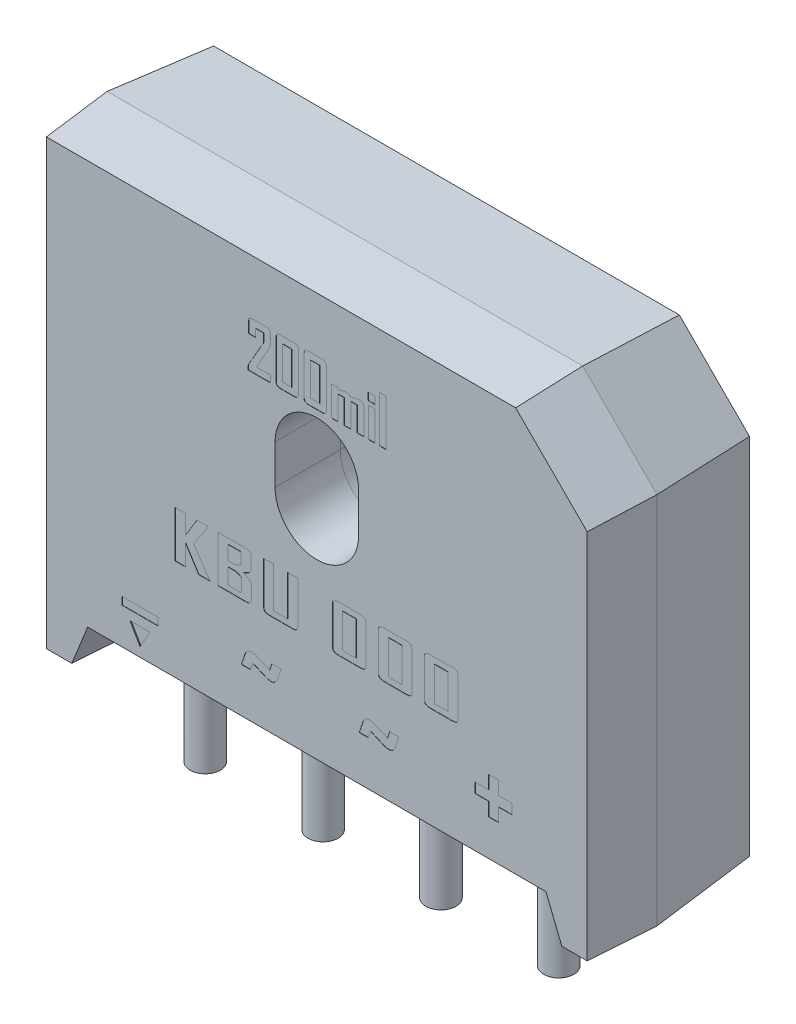
SolidWorks part; units mm, degrees
ref_plane "Спереди" through (0, 0, 0) normal (0, 0, 1) x (1, 0, 0)
ref_plane "Сверху" through (0, 0, 0) normal (0, 1, 0) x (1, 0, 0)
ref_plane "Справа" through (0, 0, 0) normal (1, 0, 0) x (0, 0, -1)
sketch "Sketch1" plane through (0, 0, 0) normal (0, 0, 1) x (1, 0, 0)
  line L0 (0, 19.3) -> (0, 0) construction
  line L1 (-4.23, 19.3) -> (19.47, 19.3)
  line L2 (-4.23, 19.3) -> (-4.23, 0)
  line L3 (-4.23, 0) -> (19.47, 0)
  line L4 (19.47, 19.3) -> (19.47, 0)
  line L5 (-4.23, 19.3) -> (19.47, 0) construction
  point P7 (7.62, 9.65)
  dimension "L" = 23.7
  dimension "H" = 19.3
  dimension "PIN_L1_H" = 0
  dimension "PIN_START" = 7.62
extrude "BODY_MAIN" add sketch "Sketch1" along normal blind 2.81 and the other way blind 4.29
sketch "Sketch8" plane through (0, 0, 2.81) normal (0, 0, 1) x (1, 0, 0)
  line L0 (7.62, 12.65) -> (7.62, 10.95) construction
  line L1 (9.42, 12.65) -> (9.42, 10.95)
  line L2 (5.82, 12.65) -> (5.82, 10.95)
  line L3 (19.47, 19.3) -> (-4.23, 19.3) construction
  line L4 (-4.23, 11.8) -> (19.47, 11.8) construction
  line L5 (-4.23, 19.3) -> (-4.23, 0) construction
  line L6 (19.47, 0) -> (19.47, 19.3) construction
  arc A0 (9.42, 12.65) -> (5.82, 12.65) centre (7.62, 12.65) ccw
  arc A1 (5.82, 10.95) -> (9.42, 10.95) centre (7.62, 10.95) ccw
  point P2 (7.62, 11.8)
  dimension "D1" = 7.5
  dimension "D2" = 3.6
  dimension "D3" = 1.7
extrude "Cut-Extrude1" cut sketch "Sketch8" against normal up to next
sketch "Sketch18" plane through (0, 0, 2.81) normal (0, 0, 1) x (1, 0, 0)
  line L0 (7.62, 0) -> (7.62, 19.3) construction
  line L1 (-4.23, 0) -> (19.47, 0) construction
  line L2 (17.364, 1.5) -> (-2.124, 1.5)
  line L3 (19.47, 19.3) -> (-4.23, 19.3) construction
  line L4 (-2.124, 1.5) -> (-2.73, 0)
  line L5 (-2.73, 0) -> (-2.73, -1)
  line L6 (-2.73, -1) -> (17.97, -1)
  line L7 (7.62, 0) -> (7.62, -1) construction
  line L8 (-4.23, 19.3) -> (-4.23, 0) construction
  line L9 (17.364, 1.5) -> (17.97, 0)
  line L10 (17.97, 0) -> (17.97, -1)
  point P14 (7.62, 1.5)
  dimension "D1" = 17.8
  dimension "D2" = 68
  dimension "D3" = 1.5
  dimension "D4" = 1
extrude "Cut-Extrude2" cut sketch "Sketch18" against normal through all
chamfer "BODY_Chamfer" distance 3.2 angle 45 1 edges at (19.47, 19.3, -0.74)
chamfer "BODY_Chamfer1" distance 2.81 angle 4 7 edges at (6.02, 19.3, 2.81) (19.47, 8.05, 2.81) (-4.23, 9.65, 2.81) (17.87, 17.7, 2.81) (17.667, 0.75, 2.81) (7.62, 1.5, 2.81) (-2.427, 0.75, 2.81) first distance on face at (6.02, 19.3, -0.74) first distance on face at (19.47, 8.05, -0.74) first distance on face at (-4.23, 9.65, -0.74) first distance on face at (17.87, 17.7, -0.74) first distance on face at (17.667, 0.75, -0.74) first distance on face at (7.62, 1.5, -0.74) first distance on face at (-2.427, 0.75, -0.74)
chamfer "BODY_Chamfer2" distance 4.29 angle 4 13 edges at (18.72, 0, -4.29) (-3.48, 0, -4.29) (19.47, 8.05, -4.29) (6.02, 19.3, -4.29) (-4.23, 9.65, -4.29) (17.87, 17.7, -4.29) (7.62, 9.15, -4.29) (5.82, 11.8, -4.29) (7.62, 14.45, -4.29) (9.42, 11.8, -4.29) (-2.427, 0.75, -4.29) (7.62, 1.5, -4.29) (17.667, 0.75, -4.29) first distance on face at (18.7226, 0, -0.4933) first distance on face at (-3.4826, 0, -0.4933) first distance on face at (19.47, 8.05, -2.145) first distance on face at (6.02, 19.3, -2.145) first distance on face at (-4.23, 9.65, -2.145) first distance on face at (17.87, 17.7, -2.145) first distance on face at (7.62, 10.05, -0.74) first distance on face at (5.82, 11.8, -0.74) first distance on face at (7.62, 13.55, -0.74) first distance on face at (9.42, 11.8, -0.74) first distance on face at (-2.427, 0.75, -2.145) first distance on face at (7.62, 1.5, -2.145) first distance on face at (17.667, 0.75, -2.145)
sketch "Sketch10" plane through (0, 0, 0) normal (0, 1, 0) x (1, 0, 0)
  circle A0 centre (0, 0) radius 0.65
  dimension "D1" = 1.3
sketch "Sketch12" plane through (0, 0, 0) normal (1, 0, 0) x (0, 0, -1)
  line L0 (0, 0) -> (0, -3.6)
  line L1 (0, 0) -> (0, 2)
  point P5 (0, 1.5)
  dimension "D1" = 3.6
sweep "PIN_straight" add profiles "Sketch10" path "Sketch12"
pattern_linear "PIN_straight_Pattern" count 4 spacing 5.08 along (1, 0, 0) of "PIN_straight"
sketch "Sketch17" plane through (0, 0, 0) normal (1, 0, 0) x (0, 0, -1)
  line L0 (1.3, -1.5) -> (7.89, -1.5)
  line L1 (0, 0) -> (0, -0.2)
  line L2 (4.29, -1.5) -> (4.29, 1.8) construction
  line L3 (0, 0) -> (0, 2)
  arc A0 (1.3, -1.5) -> (0, -0.2) centre (1.3, -0.2) cw
  point P5 (4.29, 1.8)
  dimension "D2" = 1.3
  dimension "D3" = 3.6
sweep "PIN_bent" [suppressed] add profiles "Sketch10<2>" path "Sketch17"
sketch "Sketch10<2>"
  dimension "D1" = 1.3
pattern_linear "PIN_bent_Pattern" [suppressed] count 4 spacing 5.08
sketch "Sketch5" plane through (0, 0, 2.81) normal (0, 0, 1) x (1, 0, 0)
  line L0 (-4.0335, 10.4) -> (-4.0335, 1.6965) construction
  line L1 (-4.0335, 19.1035) -> (19.2735, 19.1035) construction
  line L2 (-4.0335, 19.1035) -> (-4.0335, 1.6965) construction
  line L3 (-4.0335, 1.6965) -> (19.2735, 1.6965) construction
  line L4 (19.2735, 19.1035) -> (19.2735, 1.6965) construction
  line L5 (-4.0335, 1.6965) -> (-4.0335, 6.0482) construction
  line L6 (-4.0335, 10.4) -> (19.2735, 10.4) construction
  line L7 (-4.0335, 19.1035) -> (-4.0335, 10.4) construction
  line L8 (-4.0335, 14.7518) -> (19.2735, 14.7518) construction
  line L9 (-4.0335, 6.0482) -> (19.2735, 6.0482) construction
  line L10 (16.1886, 19.1035) -> (-4.0335, 19.1035) construction
  line L12 (-4.0335, 3.8724) -> (19.2735, 3.8724) construction
  line L13 (19.2735, 0) -> (19.2735, 16.0186) construction
  line L14 (-4.0335, 19.1035) -> (-4.0335, 0) construction
  line L15 (0, 0) -> (0, 3.8724) construction
  line L16 (-1.25, 3.8724) -> (-1.25, 1.6965) construction
  line L17 (1.25, 1.6965) -> (1.25, 3.8724) construction
  line L18 (-1.25, 3.8724) -> (1.25, 3.8724) construction
  line L20 (-1.25, 2.7844) -> (1.25, 2.7844) construction
  line L21 (3.83, 2.7844) -> (6.33, 2.7844) construction
  line L22 (8.91, 2.7844) -> (11.41, 2.7844) construction
  line L23 (13.99, 2.7844) -> (16.49, 2.7844) construction
  line L25 (-2.2565, 1.6965) -> (17.4965, 1.6965) construction
  text T0 "KBU 000" font "Agency FB" height 2
  text T1 "200mil" font "Agency FB" height 2
  text T2 "_" font "Agency FB" height 3
  text T3 "+" font "Agency FB" height 3
  text T4 "~" font "Agency FB" height 3
  text T5 "~" font "Agency FB" height 3
  point P17 (0, 0)
  dimension "D2" = 5.08
  dimension "D3" = 2.5
extrude "text" cut sketch "Sketch5" against normal blind 0.01
sketch "Sketch16" plane through (0, 0, 2.81) normal (0, 0, 1) x (1, 0, 0)
  line L0 (0, 0) -> (0, 2.5965) construction
  line L2 (0, 2.0965) -> (0.433, 2.8465)
  line L3 (0.433, 2.8465) -> (-0.433, 2.8465)
  line L4 (-0.433, 2.8465) -> (0, 2.0965)
  line L5 (-2.2565, 1.6965) -> (17.4965, 1.6965) construction
  circle A0 centre (0, 2.5965) radius 0.25 construction
  dimension "D1" = 0.5
  dimension "D2" = 0.9
extrude "pin1_mark" cut sketch "Sketch16" against normal blind 0.04
equation "\"PART_L\"= 23.7mm"
equation "\"PART_H\"= 19.3mm"
equation "\"PART_W\"= 7.1mm"
equation "\"PART_Camfer\"= 3.2mm"
equation "\"PART_PINS\"=4"
equation "\"DUMMY\"= 0"
equation "\"D1@BODY_MAIN\"= ( ( \"PIN_D\" / 2 ) + \"PIN_OFFSET\" )"
equation "\"L@Sketch1\" = \"PART_L\""
equation "\"H@Sketch1\" = \"PART_H\""
equation "\"D2@BODY_MAIN\"= \"PART_W\" - ((\"PIN_D\"/2) + \"PIN_OFFSET\")"
equation "\"PIN_D\"= 1.3mm"
equation "\"DUMMY2\"= 0"
equation "\"DUMMY3\"= 0"
equation "\"PIN_PITCH\"= 200mil"
equation "\"PIN_OFFSET\"= 2.16mm"
equation "\"D1@BODY_Chamfer\" = \"PART_Camfer\""
equation "\"PIN_START@Sketch1\" =  ( \"PIN_PITCH\" *  ( \"PART_PINS\" / 2 )  )  -  ( \"PIN_PITCH\" / 2 ) "
equation "\"PIN_L1_H\"= 0mm"
equation "\"PIN_L1_H@Sketch1\" = \"PIN_L1_H\""
equation "\"PIN_L2_H\"= \"PCB_clearance\" + \"PCB_thickness\" + \"PCB_rear\""
equation "\"DUMMY0\"= 0"
equation "\"DUMMY1\"= 0"
equation "\"PCB_clearance\"= 1mm"
equation "\"PCB_thickness\"= 1.6mm"
equation "\"PCB_rear\"= 1mm"
equation "\"D1@Sketch12\"=\"PIN_L2_H\""
equation "\"D3@Sketch17\"=\"PIN_L2_H\""
equation "\"D2@Sketch5\"=\"PIN_PITCH\""
equation "\"D1@Sketch5\"=\"PART_PINS\""
equation "\"D1@BODY_Chamfer2\"=\"D2@BODY_MAIN\""
equation "\"D1@BODY_Chamfer1\"=\"D1@BODY_MAIN\""
equation "\"D1@Sketch10\"=\"PIN_D\""
equation "\"D3@PIN_straight_Pattern\" = \"PIN_PITCH\""
equation "\"D1@PIN_straight_Pattern\" = \"PART_PINS\""
equation "\"D3@PIN_bent_Pattern\"=\"PIN_PITCH\""
equation "\"D1@PIN_bent_Pattern\"=\"PART_PINS\""
